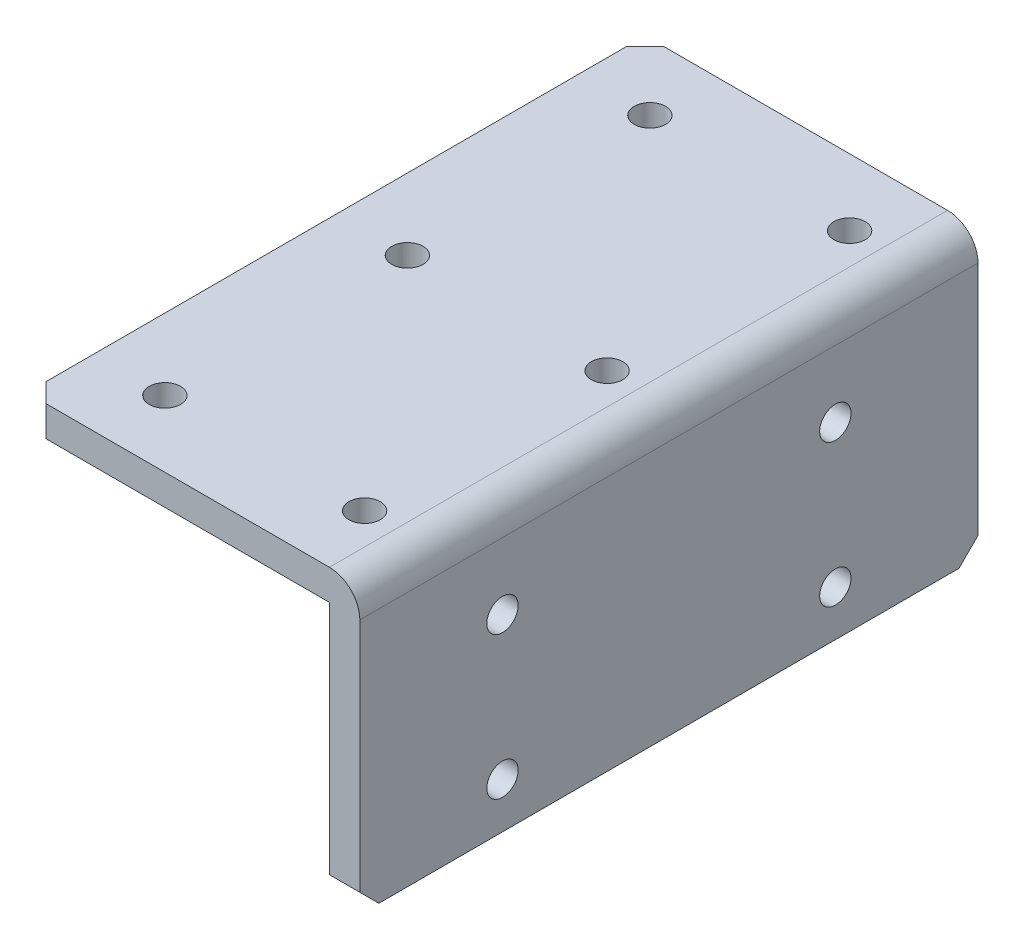
SolidWorks part; units mm, degrees
ref_plane "Front" through (0, 0, 0) normal (0, 0, 1) x (1, 0, 0)
ref_plane "Top" through (0, 0, 0) normal (0, 1, 0) x (1, 0, 0)
ref_plane "Right" through (0, 0, 0) normal (1, 0, 0) x (0, 0, -1)
sketch "Sketch1" plane through (0, 0, 0) normal (0, 0, 1) x (1, 0, 0)
  line L1 (0, -30) -> (-3.2, -30)
  line L2 (0, -30) -> (0, 0)
  line L4 (-3.2, -30) -> (-3.2, -3.2)
  line L5 (0, 0) -> (-35, 0)
  line L7 (-3.2, -3.2) -> (-35, -3.2)
  line L8 (-35, 0) -> (-35, -3.2)
  dimension "D1" = 35
  dimension "D2" = 30
  dimension "D3" = 3.2
extrude "Boss-Extrude1" add sketch "Sketch1" along normal blind 32.5 and the other way blind 32.5
fillet "Fillet1" radius 3.2 1 edges at (0, 0, 0)
hole_wizard "M4x0.7 Tapped Hole1" positions "Sketch3" profile "Sketch2" tap size "M4x0.7" standard "JIS" end condition up to next
sketch "Sketch3" plane through (0, 0, 0) normal (1, 0, 0) x (0, 0, -1)
  line L0 (0, -2.4653) -> (0, 32.0367) construction
  line L2 (-32.5, 0) -> (32.5, 0) construction
  point P0 (-17.5, -10.2)
  point P1 (-17.5, -25.2)
  point P10 (17.5, -25.2)
  point P11 (17.5, -10.2)
  dimension "D1" = 35
  dimension "D2" = 10.2
  dimension "D3" = 15
sketch "Sketch2" plane through (0, -10.2, 17.5) normal (0, 1, 0) x (0, 0, -1)
  line L0 (0, 0) -> (0, 3.2)
  line L1 (0, 3.2) -> (1.65, 3.2)
  line L2 (1.65, 3.2) -> (1.65, 0)
  line L5 (1.65, 0) -> (0, 0)
  line L11 (0, -6.35) -> (0, 107.95) construction
  dimension "Thru Tap Drill Dia." = 3.3
  dimension "Thru Tap Drill Depth" = 3.2
cosmetic thread "Hole Thread6" parameters "D1"=3.2, "D2"=4
cosmetic thread "Hole Thread7" parameters "D1"=3.2, "D2"=4
cosmetic thread "Hole Thread8" parameters "D1"=3.2, "D2"=4
cosmetic thread "Hole Thread9" parameters "D1"=3.2, "D2"=4
hole_wizard "M4x0.7 Tapped Hole2" positions "Sketch5" profile "Sketch4" tap size "M4x0.7" standard "JIS" end condition up to next
sketch "Sketch5" plane through (0, 0, 0) normal (0, 1, 0) x (-1, 0, 0)
  point P1 (6.5, 25.5)
  dimension "D1" = 6.5
  dimension "D2" = 25.5
sketch "Sketch4" plane through (-6.5, 0, 25.5) normal (1, 0, 0) x (0, 0, 1)
  line L0 (0, 0) -> (0, 3.2)
  line L1 (0, 3.2) -> (1.65, 3.2)
  line L2 (1.65, 3.2) -> (1.65, 0)
  line L5 (1.65, 0) -> (0, 0)
  line L11 (0, -6.35) -> (0, 107.95) construction
  dimension "Thru Tap Drill Dia." = 3.3
  dimension "Thru Tap Drill Depth" = 3.2
cosmetic thread "Hole Thread5" parameters "D2"=4
pattern_linear "LPattern1" count 2 spacing 21 along (-1, 0, 0) count 3 spacing 25.5 along (0, 0, -1) of "M4x0.7 Tapped Hole2"
chamfer "Chamfer1" distance 2 angle 45 4 edges at (-1.6, -30, -32.5) (-1.6, -30, 32.5) (-35, -1.6, -32.5) (-35, -1.6, 32.5)
